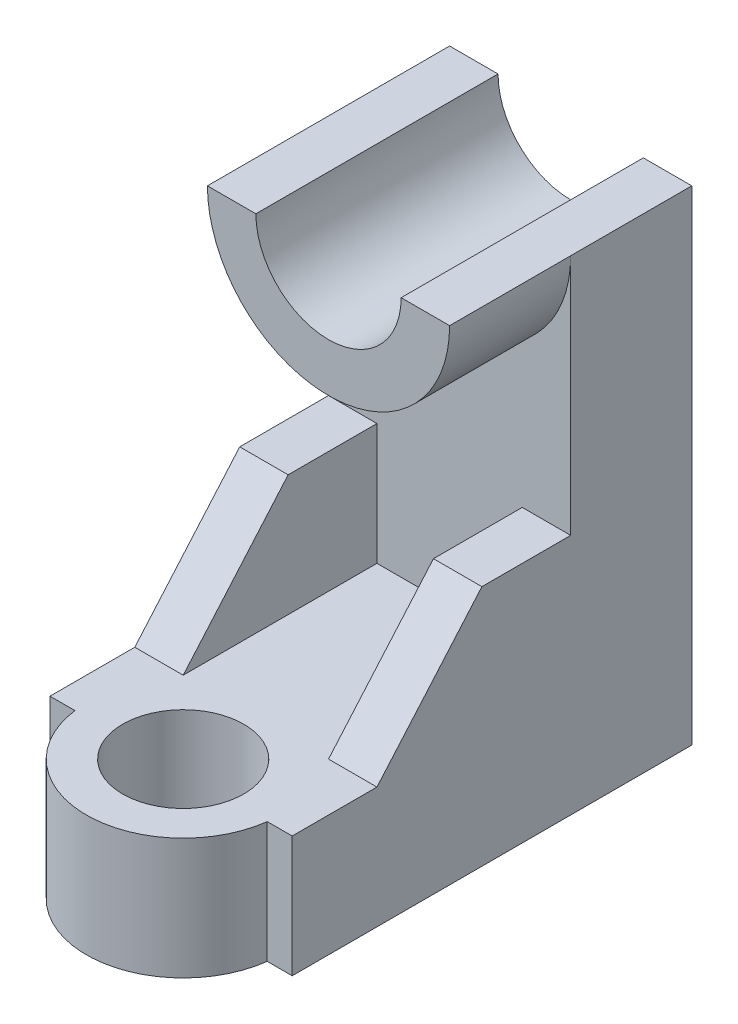
SolidWorks part; units mm, degrees
ref_plane "Front" through (0, 0, 0) normal (0, 0, 1) x (1, 0, 0)
ref_plane "Top" through (0, 0, 0) normal (0, 1, 0) x (1, 0, 0)
ref_plane "Right" through (0, 0, 0) normal (1, 0, 0) x (0, 0, -1)
sketch "Sketch1" plane through (0, 0, 0) normal (0, 0, 1) x (1, 0, 0)
  line L0 (-85.1371, -65.8236) -> (-35.1371, -65.8236)
  line L1 (-35.1371, -65.8236) -> (-35.1371, -40.8236)
  line L2 (-35.1371, -40.8236) -> (-85.1371, -40.8236)
  line L3 (-85.1371, -40.8236) -> (-85.1371, -65.8236)
  line L4 (-85.1371, -40.8236) -> (-85.1371, 34.1764)
  line L5 (-85.1371, 34.1764) -> (-75.1371, 34.1764)
  line L6 (-35.1371, 34.1764) -> (-35.1371, -40.8236)
  line L7 (-85.1371, -40.8236) -> (-85.1371, -15.8236)
  line L8 (-85.1371, -15.8236) -> (-75.1371, -15.8236)
  line L9 (-75.1371, -15.8236) -> (-75.1371, -40.8236)
  line L10 (-35.1371, -40.8236) -> (-35.1371, -15.8236)
  line L11 (-35.1371, -15.8236) -> (-45.1371, -15.8236)
  line L12 (-45.1371, -15.8236) -> (-45.1371, -40.8236)
  line L13 (-45.1371, 34.1764) -> (-35.1371, 34.1764)
  arc A0 (-85.1371, 34.1764) -> (-35.1371, 34.1764) centre (-60.1371, 34.1764) ccw
  arc A1 (-75.1371, 34.1764) -> (-45.1371, 34.1764) centre (-60.1371, 34.1764) ccw
extrude "Boss-Extrude2" add sketch "Sketch1" along normal blind 100 contours L2 L3 L0 L1 region at (-60.1371, -53.3236, 0)
extrude "Boss-Extrude3" add sketch "Sketch1<4>" along normal blind 65 contours L9 L8 L4 L2 | L11 L12 L2 L6 region at (-80.1371, -28.3236, 0) region at (-40.1371, -28.3236, 0)
sketch "Sketch1<4>" plane through (0, 0, 0) normal (0, 0, 1) x (1, 0, 0) same geometry as "Sketch1"
extrude "Boss-Extrude4" add sketch "Sketch1<5>" along normal blind 25 contours A0 L4 L8 L9 L2 L12 L11 L6 region at (-60.1371, -9.4512, 0)
sketch "Sketch1<5>" plane through (0, 0, 0) normal (0, 0, 1) x (1, 0, 0) same geometry as "Sketch1"
extrude "Boss-Extrude5" add sketch "Sketch1<6>" along normal blind 50 contours A1 L5 A0 L13 region at (-80.1371, 33.6174, 0)
sketch "Sketch1<6>" plane through (0, 0, 0) normal (0, 0, 1) x (1, 0, 0) same geometry as "Sketch1"
sketch "Sketch4" plane through (0, -40.8236, 0) normal (0, 1, 0) x (1, 0, 0)
  line L0 (-35.1371, -82.5) -> (-40.294, -82.5)
  line L2 (-35.1371, -100) -> (-35.1371, -65) construction
  line L3 (-85.1371, -100) -> (-85.1371, -65) construction
  line L4 (-79.9802, -82.5) -> (-85.1371, -82.5)
  circle A0 centre (-60.1371, -80) radius 20
  circle A1 centre (-60.1371, -80) radius 12.5
  line M7 (-85.1371, -65) -> (-85.1371, -100)
  line M8 (-85.1371, -100) -> (-35.1371, -100)
  line M9 (-35.1371, -100) -> (-35.1371, -65)
extrude "Cut-Extrude1" cut sketch "Sketch4" against normal blind 56 contours A1 | A0 L0 M8 M9 | A0 L4 M7 M8 region at (-41.0881, -40.8236, 93.3795) region at (-79.1861, -40.8236, 93.3795) region at (-60.1371, -40.8236, 80)
sketch "Sketch7" plane through (-35.1371, 0, 0) normal (1, 0, 0) x (0, 0, -1)
  line L0 (-65, -40.8236) -> (0, 34.1764)
  line L1 (-65, -40.8236) -> (-65, -15.8236)
  line L2 (-65, -15.8236) -> (-43.3333, -15.8236)
  line M7 (-25, -15.8236) -> (-65, -15.8236)
  line M8 (-65, -15.8236) -> (-65, -40.8236)
extrude "Cut-Extrude2" cut sketch "Sketch7" against normal blind 56 contours L0 M8 M7 region at (-35.1371, -24.1569, 57.7778)
